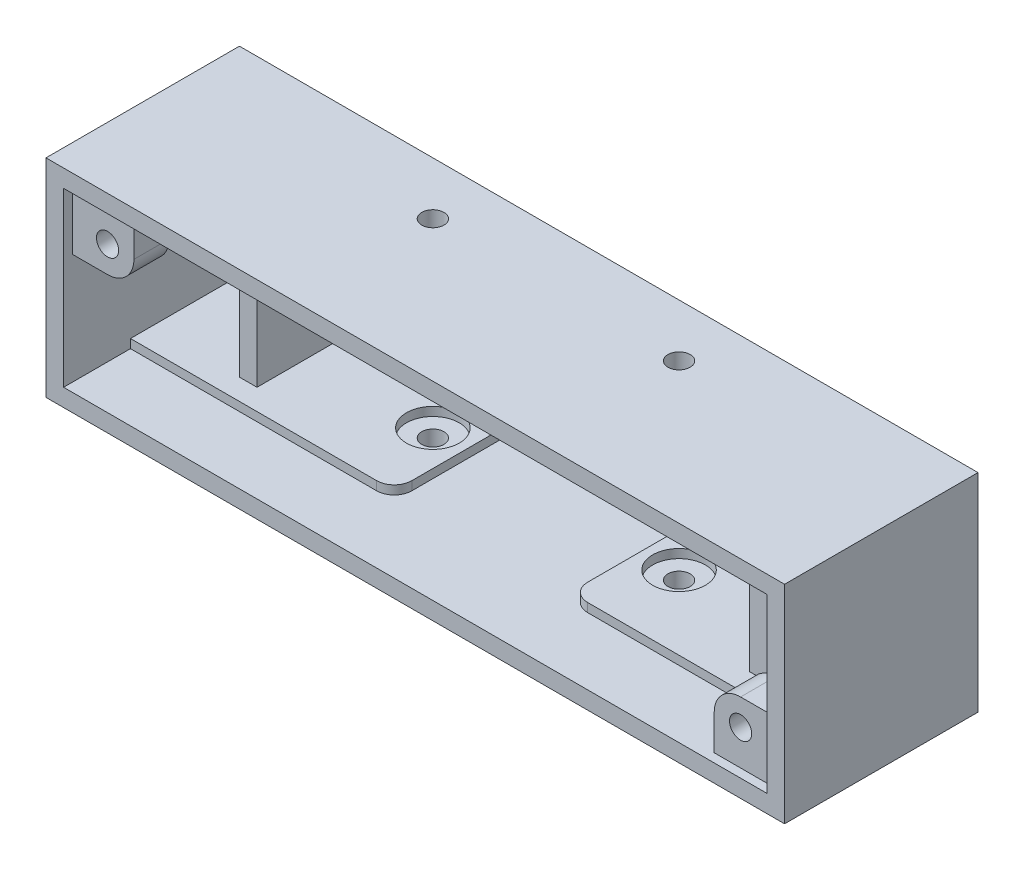
SolidWorks part; units mm, degrees
ref_plane "Front Plane" through (0, 0, 0) normal (0, 0, 1) x (1, 0, 0)
ref_plane "Top Plane" through (0, 0, 0) normal (0, 1, 0) x (1, 0, 0)
ref_plane "Right Plane" through (0, 0, 0) normal (1, 0, 0) x (0, 0, -1)
sketch "Sketch1" plane through (0, 0, 0) normal (0, 0, 1) x (1, 0, 0)
  line L1 (63.5, -15.5575) -> (-63.5, -15.5575)
  line L2 (63.5, -15.5575) -> (63.5, 15.5575)
  line L3 (63.5, 15.5575) -> (-63.5, 15.5575)
  line L4 (-63.5, -15.5575) -> (-63.5, 15.5575)
  line L5 (63.5, -15.5575) -> (-63.5, 15.5575) construction
  line L6 (63.5, 15.5575) -> (-63.5, -15.5575) construction
  point P0 (0, 0)
  dimension "D1" = 127
  dimension "D2" = 31.115
extrude "Boss-Extrude1" add sketch "Sketch1" along normal blind 3.175
sketch "Sketch2" plane through (0, 0, 3.175) normal (0, 0, 1) x (1, 0, 0)
  line L0 (-10, 0) -> (32, 0) construction
  line L1 (-10, 10.5) -> (32, 10.5)
  line L2 (-10, 10.5) -> (-10, -10.5)
  line L3 (-10, -10.5) -> (32, -10.5)
  line L4 (32, 10.5) -> (32, -10.5)
  line L6 (-13.2, 5) -> (35.2, 5) construction
  line L7 (-13.2, 5) -> (-13.2, -5) construction
  line L8 (-13.2, -5) -> (35.2, -5) construction
  line L9 (35.2, 5) -> (35.2, -5) construction
  circle A4 centre (-13.2, 5) radius 2
  circle A5 centre (-13.2, -5) radius 2
  circle A6 centre (35.2, 5) radius 2
  circle A7 centre (35.2, -5) radius 2
  point P11 (-13.2, 0)
  point P12 (11, 5)
  point P13 (11, 0)
  dimension "D6" = 4
  dimension "D1" = 42
  dimension "D2" = 21
  dimension "D3" = 10
  dimension "D4" = 10
  dimension "D5" = 48.4
extrude "Cut-Extrude1" cut sketch "Sketch2" against normal up to next
sketch "Sketch3" plane through (0, 0, 3.175) normal (0, 0, 1) x (1, 0, 0)
  line L1 (63.5, 15.5575) -> (-63.5, 15.5575)
  line L2 (63.5, 15.5575) -> (63.5, -15.5575)
  line L3 (63.5, -15.5575) -> (-63.5, -15.5575)
  line L4 (-63.5, 15.5575) -> (-63.5, -15.5575)
extrude "Extrude-Thin1" add sketch "Sketch3" along normal blind 31.75 and the other way up to surface (3.175 mm away) thin other way up to face at (37.2, -5, 0) thin type one direction wall 3.175
sketch "Sketch4" plane through (0, 0, 3.175) normal (0, 0, 1) x (1, 0, 0)
  line L0 (63.5, -15.5575) -> (63.5, 15.5575) construction
  line L1 (-63.5, -15.5575) -> (-15.875, -15.5575)
  line L2 (-63.5, -15.5575) -> (-63.5, -13.97)
  line L3 (-63.5, -13.97) -> (-15.875, -13.97)
  line L4 (63.5, -15.5575) -> (63.5, -13.97)
  line L5 (63.5, -15.5575) -> (63.5, 15.5575) construction
  line L6 (-63.5, 15.5575) -> (-15.875, 15.5575)
  line L7 (-63.5, 15.5575) -> (-63.5, 13.97)
  line L8 (-63.5, 13.97) -> (-15.875, 13.97)
  line L9 (63.5, 15.5575) -> (63.5, 13.97)
  line L10 (-15.875, -13.97) -> (-15.875, -15.5575)
  line L12 (-15.875, 15.5575) -> (-15.875, 13.97)
  line L14 (15.875, 15.5575) -> (15.875, 13.97)
  line L15 (15.875, 13.97) -> (63.5, 13.97)
  line L16 (15.875, 15.5575) -> (63.5, 15.5575)
  line L17 (15.875, -13.97) -> (15.875, -15.5575)
  line L18 (15.875, -13.97) -> (63.5, -13.97)
  line L19 (15.875, -15.5575) -> (63.5, -15.5575)
  dimension "D1" = 1.5875
  dimension "D2" = 31.75
extrude "Boss-Extrude2" add sketch "Sketch4" along normal blind 19.675
sketch "Sketch6" plane through (0, 0, 3.175) normal (0, 0, 1) x (1, 0, 0)
  line L0 (-57.15, 9.2075) -> (57.15, -9.2075) construction
  line L6 (-66.675, 18.7325) -> (-66.675, -18.7325) construction
  line L8 (66.675, 18.7325) -> (-66.675, 18.7325) construction
  circle A1 centre (-57.15, 9.2075) radius 4.7625
  circle A2 centre (57.15, -9.2075) radius 4.7625
  point P3 (0, 0)
  dimension "D2" = 9.525
  dimension "D3" = 9.525
  dimension "D1" = 9.525
extrude "Cut-Extrude2" cut sketch "Sketch6" against normal up to next
sketch "Sketch7" plane through (0, 0, 34.925) normal (0, 0, 1) x (1, 0, 0)
  line L0 (-63.5, 15.5575) -> (-63.5, 4.445)
  line L1 (-63.5, 15.5575) -> (-63.5, -15.5575) construction
  line L2 (-63.5, 4.445) -> (-57.15, 4.445)
  line L3 (-52.3875, 9.2075) -> (-52.3875, 15.5575)
  line L4 (-15.875, 15.5575) -> (-63.5, 15.5575) construction
  line L5 (-52.3875, 15.5575) -> (-63.5, 15.5575)
  line L6 (63.5, -15.5575) -> (52.3875, -15.5575)
  line L7 (-63.5, -15.5575) -> (63.5, -15.5575) construction
  line L8 (52.3875, -15.5575) -> (52.3875, -9.2075)
  line L9 (57.15, -4.445) -> (63.5, -4.445)
  line L10 (63.5, -13.97) -> (63.5, 13.97) construction
  line L11 (63.5, -4.445) -> (63.5, -15.5575)
  arc A0 (-57.15, 4.445) -> (-52.3875, 9.2075) centre (-57.15, 9.2075) ccw
  arc A3 (52.3875, -9.2075) -> (57.15, -4.445) centre (57.15, -9.2075) cw
  circle A5 centre (-57.15, 9.2075) radius 4.7625 construction
  circle A6 centre (57.15, -9.2075) radius 4.7625 construction
  point P12 (0, 0)
  point P21 (54.758, -9.2075)
  dimension "D1" = 4.7625
extrude "Boss-Extrude4" add sketch "Sketch7" against normal blind 6.35 from offset 1.5875 offset against normal yes
sketch "Sketch8" plane through (0, 0, 34.925) normal (0, 0, 1) x (1, 0, 0)
  circle A0 centre (-57.15, 9.2075) radius 2
  circle A1 centre (57.15, -9.2075) radius 2
  dimension "D1" = 4
extrude "Cut-Extrude3" cut sketch "Sketch8" against normal up to next
sketch "Sketch9" plane through (0, 0, 0) normal (0, 1, 0) x (1, 0, 0)
  line L0 (-22.225, -9.525) -> (22.225, -9.525) construction
  line L1 (-66.675, 0) -> (66.675, 0) construction
  circle A0 centre (22.225, -9.525) radius 2
  circle A1 centre (-22.225, -9.525) radius 2
  point P2 (0, -9.525)
  dimension "D3" = 4
  dimension "D1" = 9.525
  dimension "D2" = 44.45
extrude "Cut-Extrude4" cut sketch "Sketch9" against normal through all both and the other way through all
sketch "Sketch5" plane through (0, 0, 3.175) normal (0, 0, 1) x (1, 0, 0)
  line L0 (-63.5, 13.97) -> (-57.15, 13.97) construction
  line L1 (44.45, 13.97) -> (47.625, 13.97)
  line L2 (44.45, 13.97) -> (44.45, -13.97)
  line L3 (44.45, -13.97) -> (47.625, -13.97)
  line L4 (47.625, 13.97) -> (47.625, -13.97)
  line L5 (-15.875, -13.97) -> (-63.5, -13.97) construction
  line L6 (-63.5, 13.97) -> (-15.875, 13.97) construction
  line L7 (-47.625, 13.97) -> (-44.45, 13.97)
  line L8 (-47.625, 13.97) -> (-47.625, -13.97)
  line L9 (-47.625, -13.97) -> (-44.45, -13.97)
  line L10 (-44.45, 13.97) -> (-44.45, -13.97)
  line L11 (-44.45, 0) -> (44.45, 0) construction
  point P16 (0, 0)
  dimension "D1" = 3.175
  dimension "D2" = 44.45
extrude "Boss-Extrude3" add sketch "Sketch5" along normal blind 15.875
fillet "Fillet1" radius 3.175 4 edges at (-15.875, 14.7637, 22.85) (15.875, 14.7637, 22.85) (15.875, -14.7638, 22.85) (-15.875, -14.7638, 22.85)
sketch "Sketch10" plane through (0, 0, 0) normal (0, 1, 0) x (1, 0, 0)
  circle A0 centre (-22.225, -9.525) radius 4.7625
  circle A1 centre (22.225, -9.525) radius 4.7625
  dimension "D1" = 9.525
extrude "Cut-Extrude5" cut sketch "Sketch10" against normal up to surface and the other way up to surface up to face at (16.5554, -15.5575, 23.4939) other way up to face at (-16.5554, 15.5575, 23.4939)
